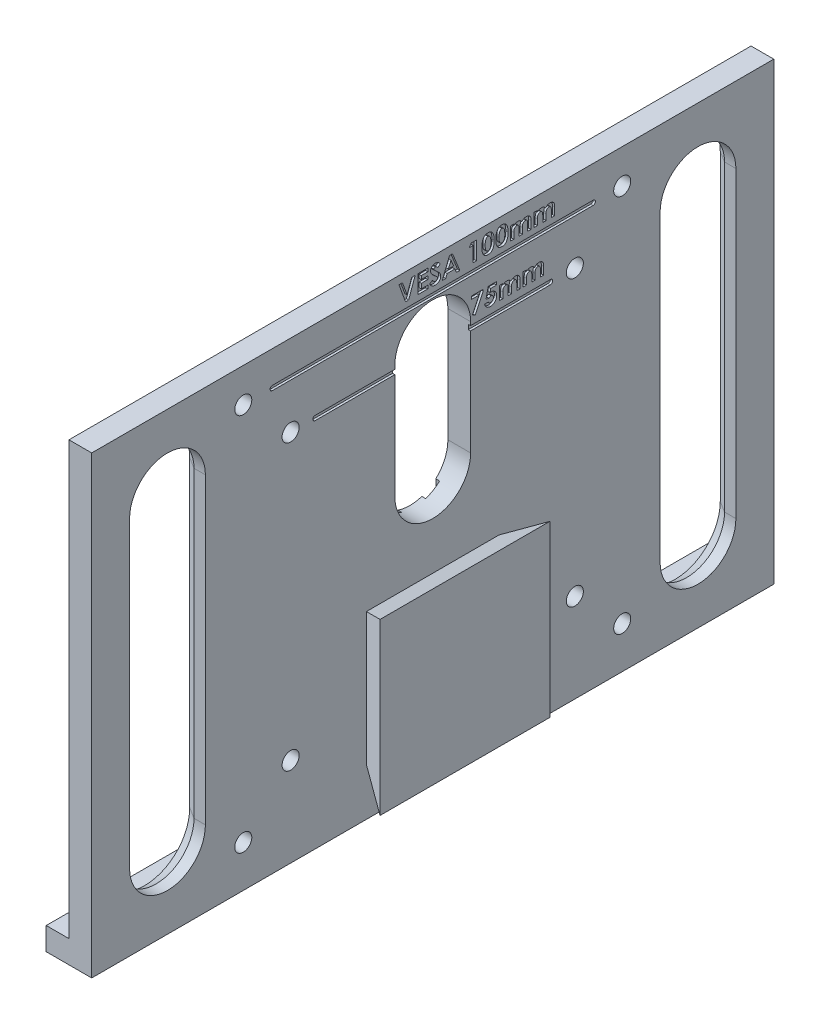
SolidWorks part; units mm, degrees
ref_plane "Front Plane" through (0, 0, 0) normal (0, 0, 1) x (1, 0, 0)
ref_plane "Top Plane" through (0, 0, 0) normal (0, 1, 0) x (1, 0, 0)
ref_plane "Right Plane" through (0, 0, 0) normal (1, 0, 0) x (0, 0, -1)
sketch "Sketch1" plane through (0, 0, 0) normal (0, 0, 1) x (1, 0, 0)
  line L0 (-12, 0) -> (0, 0)
  line L1 (0, 0) -> (0, 120)
  line L2 (0, 120) -> (-6, 120)
  line L3 (-6, 120) -> (-6, 6)
  line L4 (-6, 6) -> (-12, 6)
  line L5 (-12, 6) -> (-12, 0)
  dimension "D1" = 12
  dimension "D2" = 6
  dimension "D3" = 120
  dimension "D4" = 6
sketch "Sketch2" plane through (0, 0, 0) normal (1, 0, 0) x (0, 0, -1)
  line L0 (0, 0) -> (0, 50000) construction
  line L2 (-22.5, 52.5) -> (22.5, 52.5)
  line L3 (-22.5, 52.5) -> (-22.5, 7.5)
  line L4 (-22.5, 7.5) -> (22.5, 7.5)
  line L5 (22.5, 52.5) -> (22.5, 7.5)
  line L6 (-22.5, 52.5) -> (22.5, 7.5) construction
  line L7 (-22.5, 7.5) -> (22.5, 52.5) construction
  point P3 (0, 30)
  dimension "D1" = 45
  dimension "D2" = 45
  dimension "D3" = 30
extrude "Boss-Extrude3" add sketch "Sketch2" along normal blind 8.5
chamfer "Chamfer1" distance 5 angle 60 4 edges at (0, 7.5, 0) (0, 30, -22.5) (0, 30, 22.5) (0, 52.5, 0) first distance on face at (0, 30, 0)
extrude "Boss-Extrude4" add sketch "Sketch1" along normal blind 90 and the other way blind 90
sketch "Sketch3" plane through (0, 0, 0) normal (1, 0, 0) x (0, 0, -1)
  line L0 (0, 0) -> (0, 50000) construction
  line L1 (-70, 32.2859) -> (-70, 50032.2859) construction
  line L2 (0, 100) -> (0, 70) construction
  line L3 (10, 100) -> (10, 70)
  line L4 (-10, 100) -> (-10, 70)
  line L5 (-70, 100) -> (-70, 20) construction
  line L6 (-60, 100) -> (-60, 20)
  line L7 (-80, 100) -> (-80, 20)
  line L8 (0, 100) -> (-50000, 100) construction
  line L9 (70, 100) -> (70, 20) construction
  line L10 (60, 100) -> (60, 20)
  line L11 (80, 100) -> (80, 20)
  line L12 (90, 120) -> (-90, 120) construction
  arc A0 (10, 100) -> (-10, 100) centre (0, 100) ccw
  arc A1 (-10, 70) -> (10, 70) centre (0, 70) ccw
  arc A2 (-60, 100) -> (-80, 100) centre (-70, 100) ccw
  arc A3 (-80, 20) -> (-60, 20) centre (-70, 20) ccw
  arc A4 (60, 100) -> (80, 100) centre (70, 100) cw
  arc A5 (80, 20) -> (60, 20) centre (70, 20) cw
  point P7 (0, 85)
  point P14 (-70, 60)
  point P24 (70, 60)
  dimension "D1" = 10
  dimension "D2" = 10
  dimension "D3" = 80
  dimension "D5" = 70
  dimension "D6" = 20
extrude "hotglue slot" cut sketch "Sketch3" against normal up to surface (6 mm away) up to face at (-6, 63, 0)
sketch "Sketch4" plane through (0, 0, 0) normal (1, 0, 0) x (0, 0, -1)
  line L0 (0, 0) -> (0, 50000) construction
  line L2 (-37.5, 98.5) -> (37.5, 98.5) construction
  line L3 (-37.5, 98.5) -> (-37.5, 23.5) construction
  line L4 (-37.5, 23.5) -> (37.5, 23.5) construction
  line L5 (37.5, 98.5) -> (37.5, 23.5) construction
  line L6 (-37.5, 98.5) -> (37.5, 23.5) construction
  line L7 (-37.5, 23.5) -> (37.5, 98.5) construction
  line L8 (50, 11) -> (-50, 11) construction
  line L9 (50, 11) -> (50, 111) construction
  line L10 (50, 111) -> (-50, 111) construction
  line L11 (-50, 11) -> (-50, 111) construction
  line L12 (50, 11) -> (-50, 111) construction
  line L13 (50, 111) -> (-50, 11) construction
  circle A0 centre (-50, 111) radius 2.25
  circle A1 centre (50, 111) radius 2.25
  circle A2 centre (50, 11) radius 2.25
  circle A3 centre (-50, 11) radius 2.25
  circle A4 centre (-37.5, 98.5) radius 2.25
  circle A5 centre (37.5, 98.5) radius 2.25
  circle A6 centre (37.5, 23.5) radius 2.25
  circle A7 centre (-37.5, 23.5) radius 2.25
  point P3 (0, 61)
  point P8 (0, 61)
  point P23 (0, 61)
  point P30 (0, 61)
  dimension "D1" = 4.5
  dimension "D3" = 4.5
  dimension "D2" = 4
  dimension "D5" = 61
  dimension "D6" = 100
  dimension "D7" = 75
  dimension "D4" = 4
extrude "vesa hole" cut sketch "Sketch4" against normal up to surface (6 mm away) up to face at (-6, 60, -70)
sketch "Sketch5" plane through (0, 0, 0) normal (1, 0, 0) x (0, 0, -1)
  line L0 (-50, 111) -> (49950, 111) construction
  line L1 (-37.5, 98.5) -> (49962.5, 98.5) construction
  line L2 (0, 0) -> (0, 50000) construction
  line L3 (-42.3231, 111) -> (42.3231, 111) construction
  line L4 (-42.3231, 111.6) -> (42.3231, 111.6)
  line L5 (-42.3231, 110.4) -> (42.3231, 110.4)
  line L6 (-31.0647, 98.5) -> (31.0647, 98.5) construction
  line L7 (-31.0647, 99.1) -> (31.0647, 99.1)
  line L8 (-31.0647, 97.9) -> (31.0647, 97.9)
  arc A0 (-42.3231, 111.6) -> (-42.3231, 110.4) centre (-42.3231, 111) ccw
  arc A1 (42.3231, 110.4) -> (42.3231, 111.6) centre (42.3231, 111) ccw
  arc A2 (-31.0647, 99.1) -> (-31.0647, 97.9) centre (-31.0647, 98.5) ccw
  arc A3 (31.0647, 97.9) -> (31.0647, 99.1) centre (31.0647, 98.5) ccw
  text T0 "VESA 100mm" font "Century Gothic" height in points 18
  text T1 "75mm" font "Century Gothic" height in points 18
  point P13 (0, 111)
  point P19 (0, 98.5)
  dimension "D1" = 0.6
  dimension "D2" = 0.6
extrude "vesa" cut sketch "Sketch5" against normal blind 0.6
sketch "Sketch6" plane through (-6, 0, 0) normal (-1, 0, 0) x (0, 0, 1)
  line L0 (-54.9679, 31.181) -> (-54.9679, 90.1081) construction
  line L1 (-56.8094, 31.181) -> (-56.8094, 90.1081)
  line L2 (-53.1264, 31.181) -> (-53.1264, 90.1081)
  line L3 (-44.9679, 31.181) -> (-44.9679, 90.1081) construction
  line L4 (-46.8094, 31.181) -> (-46.8094, 90.1081)
  line L5 (-43.1264, 31.181) -> (-43.1264, 90.1081)
  line L6 (-34.9679, 31.181) -> (-34.9679, 90.1081) construction
  line L7 (-36.8094, 31.181) -> (-36.8094, 90.1081)
  line L8 (-33.1264, 31.181) -> (-33.1264, 90.1081)
  line L9 (-24.9679, 31.181) -> (-24.9679, 90.1081) construction
  line L10 (-26.8094, 31.181) -> (-26.8094, 90.1081)
  line L11 (-23.1264, 31.181) -> (-23.1264, 90.1081)
  line L12 (-14.9679, 31.181) -> (-14.9679, 90.1081) construction
  line L13 (-16.8094, 31.181) -> (-16.8094, 90.1081)
  line L14 (-13.1264, 31.181) -> (-13.1264, 90.1081)
  line L15 (-4.9679, 31.181) -> (-4.9679, 90.1081) construction
  line L16 (-6.8094, 31.181) -> (-6.8094, 90.1081)
  line L17 (-3.1264, 31.181) -> (-3.1264, 90.1081)
  line L18 (5.0321, 31.181) -> (5.0321, 90.1081) construction
  line L19 (3.1906, 31.181) -> (3.1906, 90.1081)
  line L20 (6.8736, 31.181) -> (6.8736, 90.1081)
  line L21 (15.0321, 31.181) -> (15.0321, 90.1081) construction
  line L22 (13.1906, 31.181) -> (13.1906, 90.1081)
  line L23 (16.8736, 31.181) -> (16.8736, 90.1081)
  line L24 (25.0321, 31.181) -> (25.0321, 90.1081) construction
  line L25 (23.1906, 31.181) -> (23.1906, 90.1081)
  line L26 (26.8736, 31.181) -> (26.8736, 90.1081)
  line L27 (35.0321, 31.181) -> (35.0321, 90.1081) construction
  line L28 (33.1906, 31.181) -> (33.1906, 90.1081)
  line L29 (36.8736, 31.181) -> (36.8736, 90.1081)
  line L30 (45.0321, 31.181) -> (45.0321, 90.1081) construction
  line L31 (43.1906, 31.181) -> (43.1906, 90.1081)
  line L32 (46.8736, 31.181) -> (46.8736, 90.1081)
  line L33 (55.0321, 31.181) -> (55.0321, 90.1081) construction
  line L34 (53.1906, 31.181) -> (53.1906, 90.1081)
  line L35 (56.8736, 31.181) -> (56.8736, 90.1081)
  line L36 (-54.9679, 31.181) -> (-44.9679, 31.181) construction
  line L37 (-29.7398, 113.1264) -> (29.7398, 113.1264) construction
  line L38 (-29.7398, 115.1521) -> (29.7398, 115.1521)
  line L39 (-29.7398, 111.1008) -> (29.7398, 111.1008)
  line L40 (-26.8736, 17.7382) -> (26.8736, 17.7382) construction
  line L41 (-26.8736, 19.7639) -> (26.8736, 19.7639)
  line L42 (-26.8736, 15.7126) -> (26.8736, 15.7126)
  arc A0 (-56.8094, 31.181) -> (-53.1264, 31.181) centre (-54.9679, 31.181) ccw
  arc A1 (-53.1264, 90.1081) -> (-56.8094, 90.1081) centre (-54.9679, 90.1081) ccw
  arc A2 (-46.8094, 31.181) -> (-43.1264, 31.181) centre (-44.9679, 31.181) ccw
  arc A3 (-43.1264, 90.1081) -> (-46.8094, 90.1081) centre (-44.9679, 90.1081) ccw
  arc A4 (-36.8094, 31.181) -> (-33.1264, 31.181) centre (-34.9679, 31.181) ccw
  arc A5 (-33.1264, 90.1081) -> (-36.8094, 90.1081) centre (-34.9679, 90.1081) ccw
  arc A6 (-26.8094, 31.181) -> (-23.1264, 31.181) centre (-24.9679, 31.181) ccw
  arc A7 (-23.1264, 90.1081) -> (-26.8094, 90.1081) centre (-24.9679, 90.1081) ccw
  arc A8 (-16.8094, 31.181) -> (-13.1264, 31.181) centre (-14.9679, 31.181) ccw
  arc A9 (-13.1264, 90.1081) -> (-16.8094, 90.1081) centre (-14.9679, 90.1081) ccw
  arc A10 (-6.8094, 31.181) -> (-3.1264, 31.181) centre (-4.9679, 31.181) ccw
  arc A11 (-3.1264, 90.1081) -> (-6.8094, 90.1081) centre (-4.9679, 90.1081) ccw
  arc A12 (3.1906, 31.181) -> (6.8736, 31.181) centre (5.0321, 31.181) ccw
  arc A13 (6.8736, 90.1081) -> (3.1906, 90.1081) centre (5.0321, 90.1081) ccw
  arc A14 (13.1906, 31.181) -> (16.8736, 31.181) centre (15.0321, 31.181) ccw
  arc A15 (16.8736, 90.1081) -> (13.1906, 90.1081) centre (15.0321, 90.1081) ccw
  arc A16 (23.1906, 31.181) -> (26.8736, 31.181) centre (25.0321, 31.181) ccw
  arc A17 (26.8736, 90.1081) -> (23.1906, 90.1081) centre (25.0321, 90.1081) ccw
  arc A18 (33.1906, 31.181) -> (36.8736, 31.181) centre (35.0321, 31.181) ccw
  arc A19 (36.8736, 90.1081) -> (33.1906, 90.1081) centre (35.0321, 90.1081) ccw
  arc A20 (43.1906, 31.181) -> (46.8736, 31.181) centre (45.0321, 31.181) ccw
  arc A21 (46.8736, 90.1081) -> (43.1906, 90.1081) centre (45.0321, 90.1081) ccw
  arc A22 (53.1906, 31.181) -> (56.8736, 31.181) centre (55.0321, 31.181) ccw
  arc A23 (56.8736, 90.1081) -> (53.1906, 90.1081) centre (55.0321, 90.1081) ccw
  arc A24 (-29.7398, 115.1521) -> (-29.7398, 111.1008) centre (-29.7398, 113.1264) ccw
  arc A25 (29.7398, 111.1008) -> (29.7398, 115.1521) centre (29.7398, 113.1264) ccw
  arc A26 (-26.8736, 19.7639) -> (-26.8736, 15.7126) centre (-26.8736, 17.7382) ccw
  arc A27 (26.8736, 15.7126) -> (26.8736, 19.7639) centre (26.8736, 17.7382) ccw
  point P2 (-54.9679, 60.6445)
  point P11 (-44.9679, 60.6445)
  point P18 (-34.9679, 60.6445)
  point P25 (-24.9679, 60.6445)
  point P32 (-14.9679, 60.6445)
  point P39 (-4.9679, 60.6445)
  point P46 (5.0321, 60.6445)
  point P53 (15.0321, 60.6445)
  point P60 (25.0321, 60.6445)
  point P67 (35.0321, 60.6445)
  point P74 (45.0321, 60.6445)
  point P81 (55.0321, 60.6445)
  point P88 (0, 113.1264)
  point P94 (0, 17.7382)
  dimension "D1" = 12
  dimension "D2" = 10
extrude "hotglue" cut sketch "Sketch6" against normal blind 1
chamfer "Chamfer2" distance 3 angle 32 8 edges at (-6, 10, 70) (-6, 60, 60) (-6, 60, 80) (-6, 110, 70) (-6, 60, -80) (-6, 110, -70) (-6, 10, -70) (-6, 60, -60) first distance on face at (-3, 15, 70) first distance on face at (-3, 60, 60) first distance on face at (-3, 60, 80) first distance on face at (-3, 105, 70) first distance on face at (-3, 60, -80) first distance on face at (-3, 105, -70) first distance on face at (-3, 15, -70) first distance on face at (-3, 60, -60)
equation "\"D2@Sketch2\"=\"D1@Sketch2\""
equation "\"D3@Sketch4\"=\"D1@Sketch4\""
